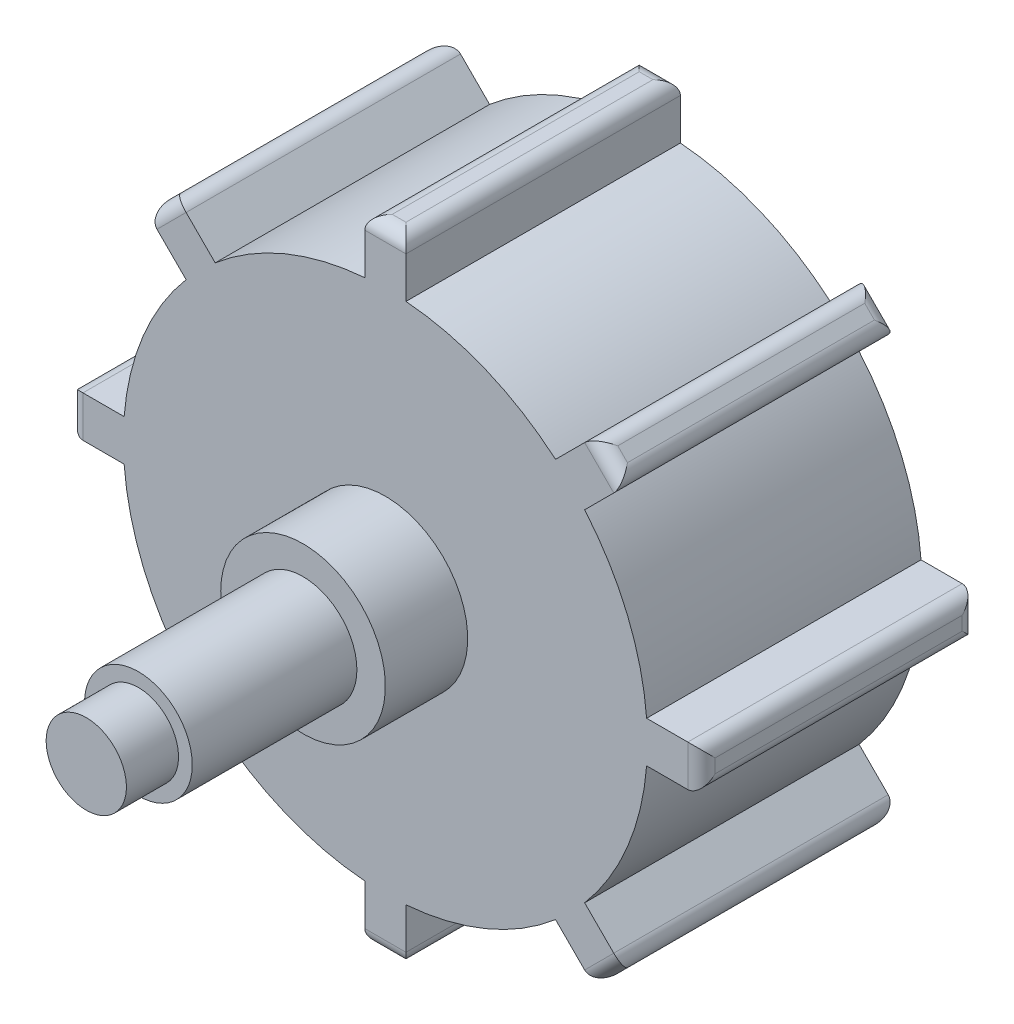
SolidWorks part; units mm, degrees
ref_plane "Ebene vorne" through (0, 0, 0) normal (0, 0, 1) x (1, 0, 0)
ref_plane "Ebene oben" through (0, 0, 0) normal (0, 1, 0) x (1, 0, 0)
ref_plane "Ebene rechts" through (0, 0, 0) normal (1, 0, 0) x (0, 0, -1)
sketch "Skizze1" plane through (0, 0, 0) normal (0, 0, 1) x (1, 0, 0)
  circle A0 centre (0, 0) radius 3.925
  dimension "D1" = 7.85
extrude "Aufsatz-Linear austragen1" add sketch "Skizze1" along normal blind 12
sketch "Skizze2" plane through (0, 0, 0) normal (0, 0, -1) x (-1, 0, 0)
  circle A0 centre (0, 0) radius 6
  dimension "D1" = 12
extrude "Aufsatz-Linear austragen2" add sketch "Skizze2" along normal blind 6
sketch "Skizze3" plane through (0, 0, -6) normal (0, 0, -1) x (-1, 0, 0)
  circle A0 centre (0, 0) radius 19.0986
  dimension "D1" = 38.1972
extrude "Aufsatz-Linear austragen3" add sketch "Skizze3" along normal blind 20
sketch "Skizze4" plane through (0, 0, -26) normal (0, 0, -1) x (-1, 0, 0)
  circle A0 centre (0, 0) radius 6.075
  dimension "D1" = 12.15
extrude "Schnitt-Linear austragen1" cut sketch "Skizze4" against normal blind 10
fillet "Verrundung1" radius 1 1 edges at (-6.075, 0, -26)
sketch "Skizze5" plane through (0, 0, -26) normal (0, 0, -1) x (-1, 0, 0)
  line L0 (0, 0) -> (0, 23.0396) construction
  line L1 (-1.5, 19.0396) -> (-1.5, 23.0396)
  line L2 (-1.5, 23.0396) -> (0, 23.0396)
  line L3 (0, 23.0396) -> (1.5, 23.0396)
  line L4 (1.5, 23.0396) -> (1.5, 19.0396)
  line L5 (-1.5, 19.0396) -> (1.5, 19.0396)
  circle A0 centre (0, 0) radius 19.0986 construction
  circle A2 centre (0, 0) radius 19.0986
  arc A3 (-1.5, 19.0396) -> (1.5, 19.0396) centre (0, 0) ccw
  circle M5 centre (0, 0) radius 19.0986
  dimension "D1" = 1.5
  dimension "D2" = 1.5
  dimension "D3" = 4
  dimension "D4" = 0
extrude "Aufsatz-Linear austragen4" add sketch "Skizze5" against normal up to surface (20 mm away) contours L0 L4 L3 M5 | L0 L2 L1 M5 region at (0.7519, 21.0592, -26) region at (-0.7519, 21.0592, -26) up to face at (-6, 0, -6)
fillet "Verrundung2" radius 1 4 edges at (1.5, 23.0396, -16) (-1.5, 23.0396, -16) (0, 23.0396, -26) (0, 23.0396, -6)
pattern_circular "Kreismuster1" count 8 over 360 about axis through (0, 0, -26) along (0, 0, 1) of "Verrundung2", "Aufsatz-Linear austragen4" reverse direction yes
sketch "Skizze6" plane through (0, 0, 12) normal (0, 0, 1) x (1, 0, 0)
  circle A0 centre (0, 0) radius 2.925
  dimension "D1" = 5.85
extrude "Aufsatz-Linear austragen5" add sketch "Skizze6" along normal blind 3.8
